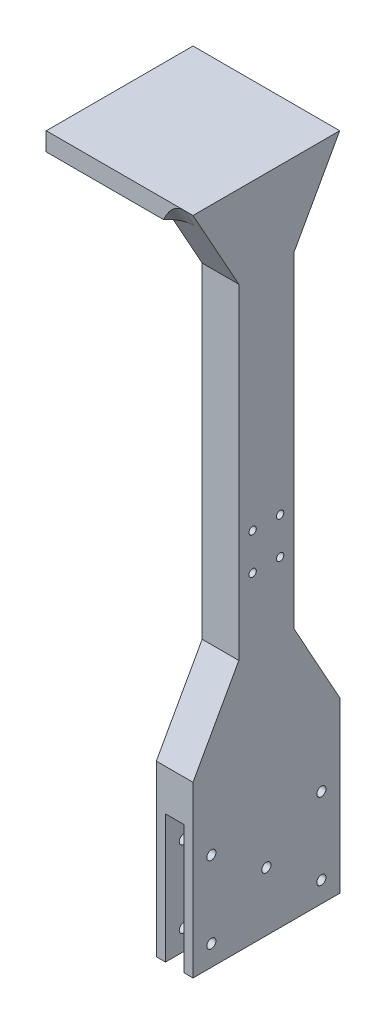
SolidWorks part; units mm, degrees
ref_plane "Plan de face" through (0, 0, 0) normal (0, 0, 1) x (1, 0, 0)
ref_plane "Plan de dessus" through (0, 0, 0) normal (0, 1, 0) x (1, 0, 0)
ref_plane "Plan de droite" through (0, 0, 0) normal (1, 0, 0) x (0, 0, -1)
sketch "Support Balise" plane through (0, 0, 0) normal (0, 0, 1) x (1, 0, 0)
  line L1 (0, 0) -> (20, 0)
  line L2 (0, 0) -> (0, 350)
  line L3 (0, 350) -> (20, 350)
  line L4 (20, 0) -> (20, 350)
  dimension "D1" = 20
  dimension "D2" = 350
extrude "Support balise bossage" add sketch "Support Balise" along normal blind 80
sketch "Esquisse3" plane through (0, 350, 0) normal (0, 1, 0) x (1, 0, 0)
  line L0 (20, 0) -> (20, -80)
  line L1 (20, -80) -> (-60, -80)
  line L2 (-60, -80) -> (-60, 0)
  line L3 (-60, 0) -> (20, 0)
  dimension "D1" = 80
extrude "Support Cheval enlevement de matiere" add sketch "Esquisse3" along normal blind 10
sketch "Esquisse8" plane through (0, 0, 80) normal (0, 0, 1) x (1, 0, 0)
  line L0 (0, 350) -> (0, 0) construction
  line L1 (5, 70) -> (15, 70)
  line L2 (5, 70) -> (5, 0)
  line L3 (5, 0) -> (15, 0)
  line L4 (15, 70) -> (15, 0)
  line L5 (20, 0) -> (20, 360) construction
  line L6 (0, 0) -> (20, 0) construction
  point P4 (5, 35)
  point P11 (10, 0)
  dimension "D1" = 5
  dimension "D2" = 5
  dimension "D3" = 0
  dimension "D4" = 70
extrude "Support Cheval" cut sketch "Esquisse8" against normal up to surface (80 mm away) up to face at (-13.3333, 236.6667, 0)
sketch "Serrage vis" plane through (5, 0, 0) normal (1, 0, 0) x (0, 0, -1)
  line L0 (-80, 0) -> (-80, 360) construction
  line L1 (0, 0) -> (0, 360) construction
  line L2 (-70, 53.0572) -> (-10, 11.2846) construction
  line L3 (-10, 53.0572) -> (-70, 11.2846) construction
  circle A0 centre (-70, 11.2846) radius 2.5
  circle A1 centre (-70, 53.0572) radius 2.5
  circle A2 centre (-10, 53.0572) radius 2.5
  circle A3 centre (-10, 11.2846) radius 2.5
  circle A4 centre (-40, 32.1709) radius 2.5
  dimension "D1" = 5
  dimension "D2" = 5
  dimension "D3" = 5
  dimension "D4" = 5
  dimension "D9" = 5
  dimension "D5" = 10
  dimension "D6" = 10
  dimension "D7" = 10
  dimension "D8" = 10
extrude "Vis" cut sketch "Serrage vis" against normal up to surface and the other way through all up to face at (0, 175, 40)
sketch "Design" plane through (20, 0, 0) normal (1, 0, 0) x (0, 0, -1)
  line L0 (-40, 360) -> (-40, 0) construction
  line L1 (-80, 360) -> (0, 360) construction
  line L2 (-80, 0) -> (0, 0) construction
  line L3 (-80, 360) -> (-55, 315)
  line L4 (0, 360) -> (-25, 315)
  line L5 (-80, 92.4061) -> (-55, 137.4061)
  line L6 (-80, 0) -> (-80, 360) construction
  line L7 (-25, 315) -> (-25, 137.4061)
  line L8 (-55, 315) -> (-55, 137.4061)
  line L9 (-80, 360) -> (-80, 92.4061)
  line L10 (0, 92.4061) -> (-25, 137.4061)
extrude "Enlèv. mat.-Extru.5" cut sketch "Design" against normal up to surface (20 mm away) contours L8 L3 L7 L5 | L10 L4 L7
fillet "Pour Impression" radius 15 2 edges at (0, 355, 2.7778) (0, 355, 77.2222)
sketch "Fixation pour assemblage" plane through (20, 0, 0) normal (1, 0, 0) x (0, 0, -1)
  line L0 (-55, 185) -> (-25, 185) construction
  line L1 (-55, 315) -> (-55, 137.4061) construction
  line L2 (-25, 315) -> (-25, 137.4061) construction
  line L3 (-80, 360) -> (0, 360) construction
  line L5 (-40, 360) -> (-40, 0) construction
  line L6 (-80, 0) -> (0, 0) construction
  circle A0 centre (-47.5, 195) radius 2
  circle A1 centre (-32.5, 195) radius 2
  circle A2 centre (-32.5, 175) radius 2
  circle A3 centre (-47.5, 175) radius 2
  dimension "D4" = 4
  dimension "D1" = 175
  dimension "D2" = 7.5
  dimension "D3" = 10
extrude "Vis pour Assemblage" cut sketch "Fixation pour assemblage" against normal up to surface (20 mm away) up to face at (0, 53.0572, 67.5)
sketch "Esquisse13" plane through (20, 0, 0) normal (1, 0, 0) x (0, 0, -1)
  line L0 (-55, 185) -> (-25, 185) construction
  line L1 (-55, 315) -> (-55, 137.4061) construction
  line L2 (-25, 315) -> (-25, 137.4061) construction
  line L3 (-80, 360) -> (0, 360) construction
  line L4 (-174.8974, 185) -> (122.4543, 185)
  line L5 (122.4543, 185) -> (122.4543, 440.4204)
  line L6 (122.4543, 440.4204) -> (-174.8974, 440.4204)
  line L7 (-174.8974, 440.4204) -> (-174.8974, 185)
  line L8 (-174.8974, 185) -> (-175.6186, 187.9975)
  dimension "D1" = 175
